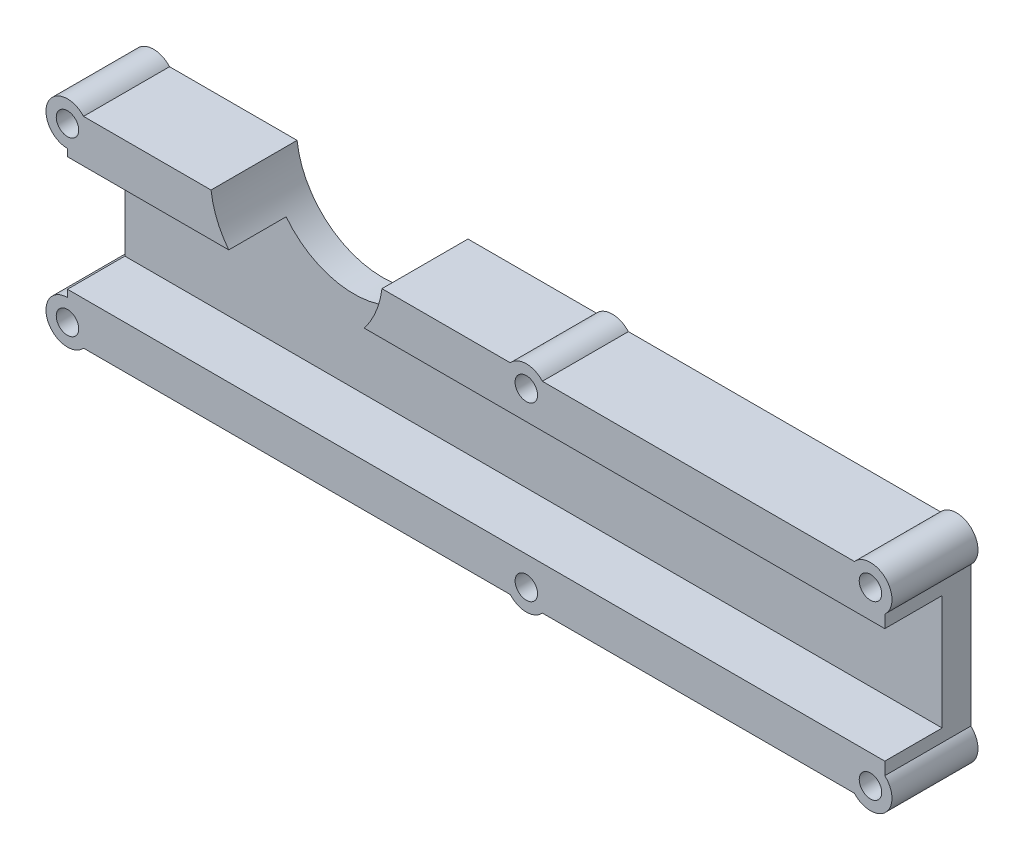
SolidWorks part; units mm, degrees
material "Nylon 101"
ref_plane "Front Plane" through (0, 0, 0) normal (0, 0, 1) x (1, 0, 0)
ref_plane "Top Plane" through (0, 0, 0) normal (0, 1, 0) x (1, 0, 0)
ref_plane "Right Plane" through (0, 0, 0) normal (1, 0, 0) x (0, 0, -1)
sketch "Sketch1" plane through (0, 0, 0) normal (0, 0, 1) x (1, 0, 0)
  line L0 (0, 38.1) -> (76.2, 38.1) construction
  line L1 (3.5498, -3.175) -> (72.6502, -3.175)
  line L3 (3.5498, 41.275) -> (72.6502, 41.275)
  line L4 (79.375, 3.5498) -> (79.375, 34.5502)
  line L5 (76.2, 0) -> (76.2, 38.1) construction
  line L6 (0, 0) -> (76.2, 0) construction
  line L8 (-3.175, 41.275) -> (79.375, 41.275) construction
  line L9 (-3.175, -3.175) -> (-3.175, 41.275) construction
  line L10 (-3.175, -3.175) -> (79.375, -3.175) construction
  line L11 (79.375, -3.175) -> (79.375, 41.275) construction
  line L12 (-3.5498, 41.275) -> (-31.9729, 41.275)
  line L13 (0, 0) -> (-101.6, 0) construction
  line L15 (0, 38.1) -> (-101.6, 38.1) construction
  line L17 (-101.6, 4.7625) -> (-101.6, 33.3375)
  line L18 (-98.0502, -3.175) -> (-3.5498, -3.175)
  line L19 (-69.8127, 41.275) -> (-98.0502, 41.275)
  line L20 (0, 0) -> (0, 38.1) construction
  circle A4 centre (0, 38.1) radius 2.4892
  circle A5 centre (0, 0) radius 2.4892
  circle A6 centre (76.2, 38.1) radius 2.4892
  circle A7 centre (76.2, 0) radius 2.4892
  arc A8 (3.5498, 41.275) -> (-3.5498, 41.275) centre (0, 38.1) ccw
  arc A9 (-3.5498, -3.175) -> (3.5498, -3.175) centre (0, 0) ccw
  arc A10 (72.6502, -3.175) -> (79.375, 3.5498) centre (76.2, 0) ccw
  arc A11 (79.375, 34.5502) -> (72.6502, 41.275) centre (76.2, 38.1) ccw
  circle A12 centre (-101.6, 38.1) radius 2.4892
  circle A14 centre (-101.6, 0) radius 2.4892
  arc A15 (-98.0502, 41.275) -> (-101.6, 33.3375) centre (-101.6, 38.1) ccw
  arc A16 (-101.6, 4.7625) -> (-98.0502, -3.175) centre (-101.6, 0) ccw
  arc A17 (-69.8127, 41.275) -> (-31.9729, 41.275) centre (-50.8928, 43.4975) ccw
  point P20 (-35.5701, 19.05)
  dimension "D3" = 4.9784
  dimension "D5" = 9.525
  dimension "D7" = 38.1
  dimension "D1" = 38.1
  dimension "D2" = 76.2
  dimension "D6" = 101.6
  dimension "D8" = 50.8928
  dimension "D9" = 5.3975
  dimension "D4" = 3.175
extrude "Boss-Extrude1" add sketch "Sketch1" along normal blind 19.05 contours L1 L4 L3 A7 A6 A5 A4 | A8 A4 | A9 A5 | A10 A7 | A11 A6 region at (-9.1746, 18.078, 0)
sketch "Sketch2" plane through (-101.6, 0, 0) normal (-1, 0, 0) x (0, 0, 1)
  line L0 (0, 4.7625) -> (0, 33.3375) construction
  line L16 (0, 31.75) -> (0, 6.35)
  line L17 (0, 6.35) -> (12.7, 6.35)
  line L18 (12.7, 6.35) -> (12.7, 31.75)
  line L19 (12.7, 31.75) -> (0, 31.75)
  point P3 (0, 19.05)
  point P9 (0, 19.05)
  dimension "D1" = 12.7
  dimension "D2" = 25.4
extrude "Cut-Extrude1" cut sketch "Sketch2" against normal through all
mirror "Mirror1" about plane through (0, 0, 19.05) normal (0, 0, 1) of bodies 103
delete or keep bodies "Body-Delete/Keep 1" type delete bodies bodies 103
